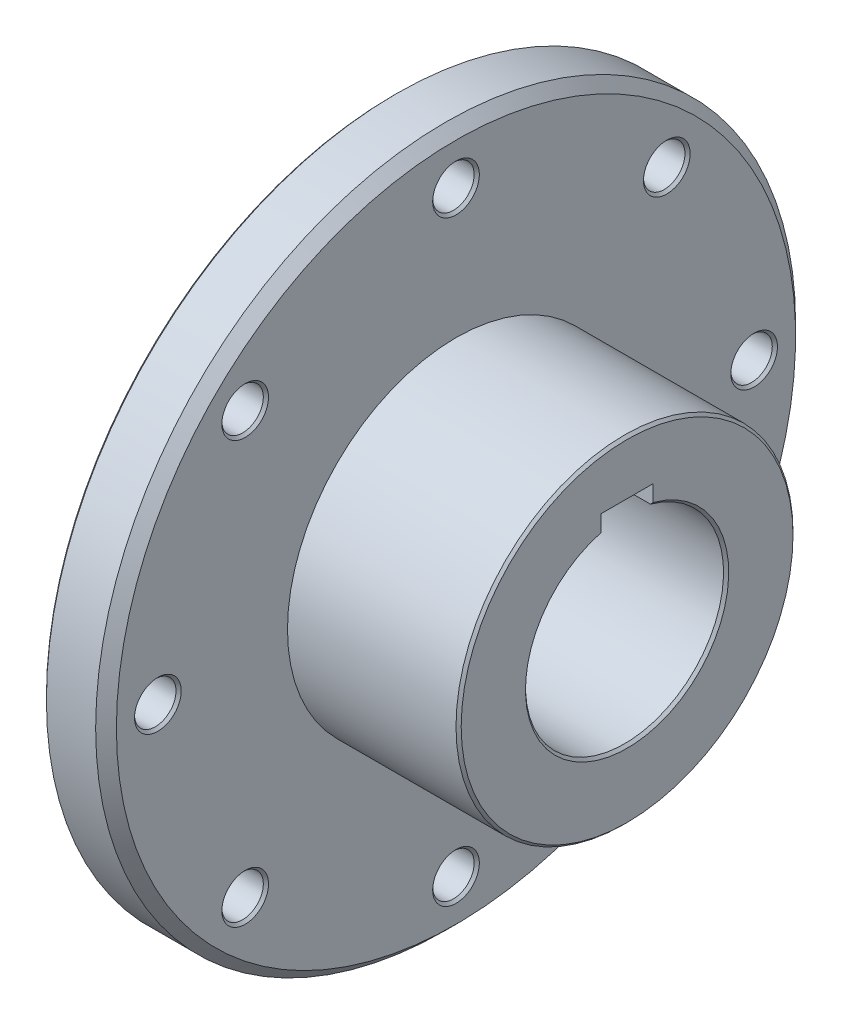
SolidWorks part; units mm, degrees
ref_plane "前视基准面" through (0, 0, 0) normal (0, 0, 1) x (1, 0, 0)
ref_plane "上视基准面" through (0, 0, 0) normal (0, 1, 0) x (1, 0, 0)
ref_plane "右视基准面" through (0, 0, 0) normal (1, 0, 0) x (0, 0, -1)
other "Configuration Table"
sketch "草图1" plane through (0, 0, 0) normal (0, 0, 1) x (1, 0, 0)
  line L0 (0, 0) -> (144.6131, 0) construction
  line L1 (0, 19.1) -> (0, 32.5)
  line L2 (0, 32.5) -> (10, 32.5)
  line L3 (10, 32.5) -> (10, 67.5)
  line L4 (10, 67.5) -> (22, 67.5)
  line L5 (22, 67.5) -> (22, 32.5)
  line L6 (22, 32.5) -> (55, 32.5)
  line L7 (55, 32.5) -> (55, 19.1)
  line L8 (55, 19.1) -> (0, 19.1)
  dimension "D1" = 135
  dimension "D2" = 55
  dimension "D3" = 10
  dimension "D4" = 22
  dimension "D5" = 65
  dimension "D6" = 38.2
revolve "旋转1" add sketch "草图1" angle 360 about L0
sketch "草图2" plane through (55, 0, 0) normal (1, 0, 0) x (0, 0, -1)
  line L1 (-5, 22.1) -> (5, 22.1)
  line L2 (-5, 22.1) -> (-5, 0)
  line L3 (-5, 0) -> (5, 0)
  line L4 (5, 22.1) -> (5, 0)
  line L5 (-5, 22.1) -> (5, 0) construction
  line L6 (-5, 0) -> (5, 22.1) construction
  circle A1 centre (0, 0) radius 19.1 construction
  point P0 (0, 11.05)
  dimension "D1" = 3
  dimension "D2" = 10
extrude "切除-拉伸1" cut sketch "草图2" against normal through all
sketch "草图3" plane through (22, 0, 0) normal (1, 0, 0) x (0, 0, -1)
  circle A0 centre (0, 0) radius 57.5 construction
  circle A1 centre (0, 57.5) radius 4
  circle A2 centre (40.6586, 40.6586) radius 4
  circle A3 centre (57.5, 0) radius 4
  circle A4 centre (40.6586, -40.6586) radius 4
  circle A5 centre (0, -57.5) radius 4
  circle A6 centre (-40.6586, -40.6586) radius 4
  circle A7 centre (-57.5, 0) radius 4
  circle A8 centre (-40.6586, 40.6586) radius 4
  point P21 (0, 0)
  dimension "D1" = 115
  dimension "D2" = 8
  dimension "D3" = 8
extrude "切除-拉伸2" cut sketch "草图3" against normal through all
chamfer "倒角1" distance 2 angle 45 1 edges at (22, 0, 67.5)
chamfer "倒角2" distance 1 angle 45 1 edges at (0, -19.1, 0)
chamfer "倒角3" distance 0.5 angle 45 19 edges at (55, 0, 32.5) (10, 0, 67.5) (10, 40.6586, 36.6586) (10, 0, 53.5) (10, -40.6586, 36.6586) (10, -57.5, -4) (10, -40.6586, -44.6586) (10, 0, -61.5) (10, 40.6586, -44.6586) (10, 57.5, -4) (22, 40.6586, 36.6586) (22, 57.5, -4) (22, 0, -61.5) (22, 40.6586, -44.6586) (22, -40.6586, -44.6586) (22, -57.5, -4) (22, -40.6586, 36.6586) (22, 0, 53.5) (55, -19.1, 0)
